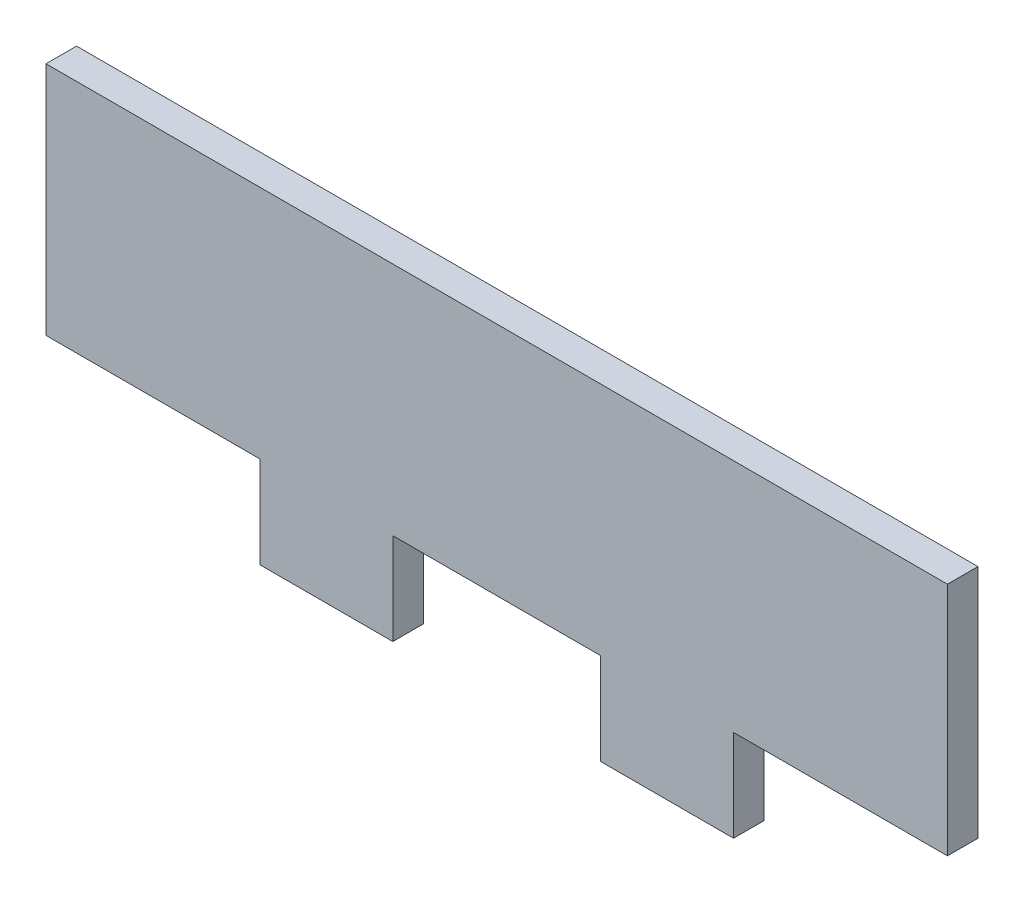
SolidWorks part; units mm, degrees
ref_plane "Front Plane" through (0, 0, 0) normal (0, 0, 1) x (1, 0, 0)
ref_plane "Top Plane" through (0, 0, 0) normal (0, 1, 0) x (1, 0, 0)
ref_plane "Right Plane" through (0, 0, 0) normal (1, 0, 0) x (0, 0, -1)
sketch "Sketch1" plane through (0, 0, 0) normal (0, 0, 1) x (1, 0, 0)
  line L1 (-73.75, 26.75) -> (73.75, 26.75)
  line L2 (-73.75, 26.75) -> (-73.75, -26.75)
  line L3 (-73.75, -26.75) -> (73.75, -26.75)
  line L4 (73.75, 26.75) -> (73.75, -26.75)
  line L5 (-73.75, 26.75) -> (73.75, -26.75) construction
  line L6 (-73.75, -26.75) -> (73.75, 26.75) construction
  point P0 (0, 0)
  dimension "D1" = 147.5
  dimension "D2" = 53.5
extrude "Boss-Extrude1" add sketch "Sketch1" along normal blind 5
sketch "Sketch2" plane through (0, 0, 0) normal (0, 0, -1) x (-1, 0, 0)
  line L0 (73.75, 26.75) -> (73.75, -26.75) construction
  line L1 (-73.75, 26.75) -> (73.75, 26.75) construction
  circle A0 centre (12.5, 9.25) radius 5
  circle A1 centre (-12.5, 9.25) radius 5
  dimension "D1" = 10
  dimension "D2" = 61.25
  dimension "D3" = 17.5
  dimension "D4" = 2
extrude "Boss-Extrude2" add sketch "Sketch2" along normal blind 7
sketch "Sketch3" plane through (0, 0, 5) normal (0, 0, 1) x (1, 0, 0)
  line L0 (0, 0) -> (0, 50.6331) construction
  line L1 (-73.75, -26.75) -> (-38.75, -26.75)
  line L2 (-73.75, -26.75) -> (-73.75, -11.75)
  line L3 (-73.75, -11.75) -> (-38.75, -11.75)
  line L4 (-38.75, -26.75) -> (-38.75, -11.75)
  line L5 (38.75, -26.75) -> (38.75, -11.75)
  line L6 (73.75, -11.75) -> (38.75, -11.75)
  line L7 (73.75, -26.75) -> (73.75, -11.75)
  line L8 (73.75, -26.75) -> (38.75, -26.75)
  dimension "D1" = 35
  dimension "D2" = 15
extrude "Cut-Extrude1" cut sketch "Sketch3" against normal through all
sketch "Sketch4" plane through (0, 0, 5) normal (0, 0, 1) x (1, 0, 0)
  line L8 (38.75, -11.75) -> (38.75, -26.75) construction
  line L9 (-17, -11.75) -> (17, -11.75)
  line L10 (-17, -11.75) -> (-17, -26.75)
  line L11 (-17, -26.75) -> (17, -26.75)
  line L12 (17, -11.75) -> (17, -26.75)
  line L13 (73.75, 26.75) -> (-73.75, 26.75) construction
  line L14 (-38.75, -26.75) -> (38.75, -26.75) construction
  line L15 (-38.75, -26.75) -> (-38.75, -11.75) construction
  dimension "D1" = 21.75
  dimension "D2" = 38.5
  dimension "D3" = 0
  dimension "D4" = 21.75
extrude "Cut-Extrude2" cut sketch "Sketch4" against normal blind 10
